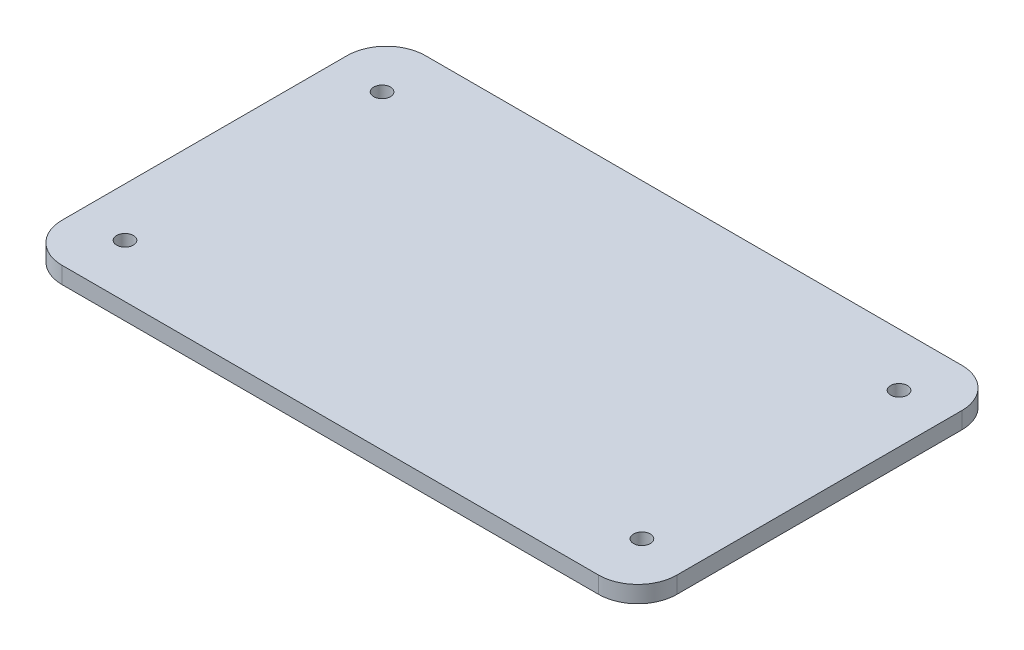
SolidWorks part; units mm, degrees
ref_plane "Front Plane" through (0, 0, 0) normal (0, 0, 1) x (1, 0, 0)
ref_plane "Top Plane" through (0, 0, 0) normal (0, 1, 0) x (1, 0, 0)
ref_plane "Right Plane" through (0, 0, 0) normal (1, 0, 0) x (0, 0, -1)
sketch "Sketch1" plane through (0, 0, 0) normal (0, 1, 0) x (1, 0, 0)
  line L1 (48, -32.5) -> (-48, -32.5)
  line L2 (55, -25.5) -> (55, 25.5)
  line L3 (48, 32.5) -> (-48, 32.5)
  line L4 (-55, -25.5) -> (-55, 25.5)
  line L5 (55, -32.5) -> (-55, 32.5) construction
  line L6 (55, 32.5) -> (-55, -32.5) construction
  line L7 (46.25, -23) -> (-46.25, -23) construction
  line L8 (46.25, -23) -> (46.25, 23) construction
  line L9 (46.25, 23) -> (-46.25, 23) construction
  line L10 (-46.25, -23) -> (-46.25, 23) construction
  line L11 (46.25, -23) -> (-46.25, 23) construction
  line L12 (46.25, 23) -> (-46.25, -23) construction
  circle A0 centre (-46.25, 23) radius 1.5
  circle A1 centre (-46.25, -23) radius 1.5
  circle A2 centre (46.25, -23) radius 1.5
  circle A3 centre (46.25, 23) radius 1.5
  arc A4 (-48, -32.5) -> (-55, -25.5) centre (-48, -25.5) cw
  arc A5 (48, -32.5) -> (55, -25.5) centre (48, -25.5) ccw
  arc A6 (55, 25.5) -> (48, 32.5) centre (48, 25.5) ccw
  arc A7 (-48, 32.5) -> (-55, 25.5) centre (-48, 25.5) ccw
  point P0 (0, 0)
  point P6 (0, 0)
  dimension "D5" = 7
  dimension "D1" = 110
  dimension "D2" = 65
  dimension "D3" = 92.5
  dimension "D4" = 46
extrude "Boss-Extrude1" add sketch "Sketch1" along normal mid plane 3
